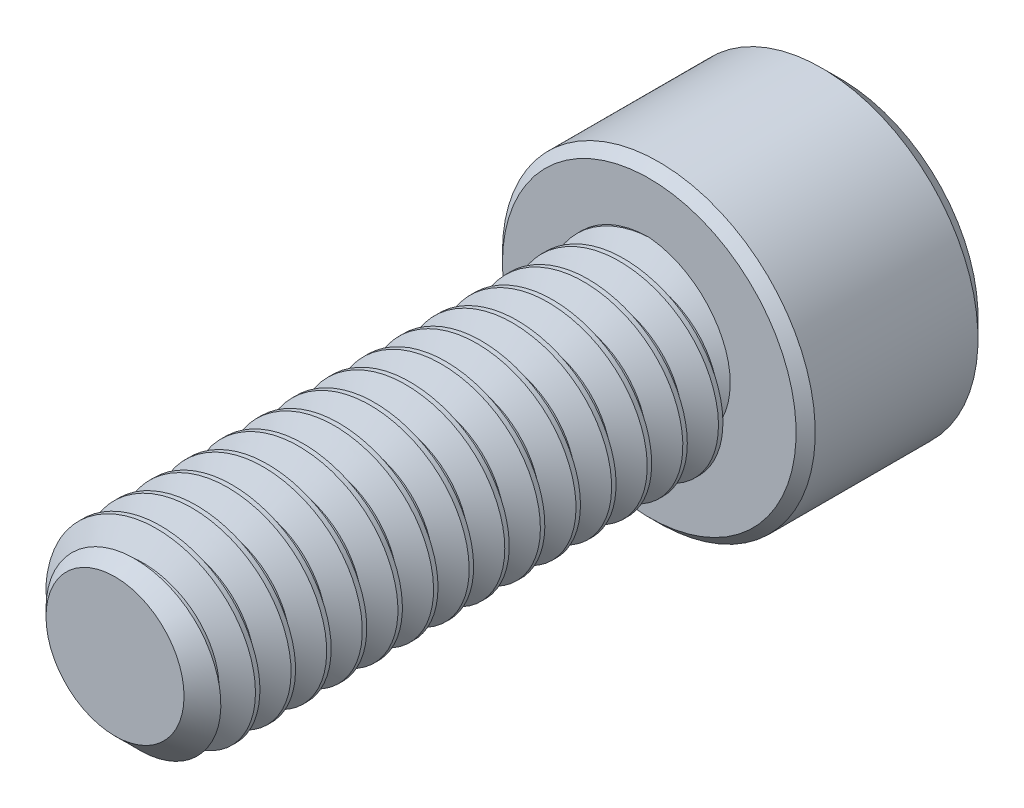
SolidWorks part; units mm, degrees
ref_plane "Front Plane" through (0, 0, 0) normal (0, 0, 1) x (1, 0, 0)
ref_plane "Top Plane" through (0, 0, 0) normal (0, 1, 0) x (1, 0, 0)
ref_plane "Right Plane" through (0, 0, 0) normal (1, 0, 0) x (0, 0, -1)
sketch "Sketch1" plane through (0, 0, 0) normal (0, 0, 1) x (1, 0, 0)
  line L0 (0, 1.4224) -> (0, -1.4224) construction
  circle A0 centre (0, 0) radius 1.4224
  dimension "OD" = 2.8448
extrude "Extrude1" add sketch "Sketch1" against normal blind 7.9375
sketch "Sketch2" plane through (0, 0, 0) normal (0, 0, 1) x (1, 0, 0)
  circle A0 centre (0, 0) radius 1.4224 construction
  circle A1 centre (0, 0) radius 1.4224
curve "Helix/Spiral1" pitch 0.5292 height 8.4667 radius 1.4224 centre (0, 0, 0) axis (0, 0, -1) start towards (0, 1, 0) parameters "pitch"=0.5292
chamfer "Chamfer3" distance 0.3969 angle 45 1 edges at (1.4224, 0, 0)
sketch "Sketch3" plane through (0, 0, 0) normal (1, 0, 0) x (0, 0, -1)
  line L0 (-0.463, 1.4224) -> (-0.2646, 1.0787)
  line L1 (-0.2646, 1.0787) -> (-0.1984, 1.0787)
  line L2 (-0.1984, 1.0787) -> (0, 1.4224)
  line L3 (-0.463, 1.4224) -> (0, 1.4224)
  line L4 (-0.2315, 1.4224) -> (-0.2315, 1.0787) construction
  line L5 (-0.3638, 1.2505) -> (-0.0992, 1.2505) construction
  line L6 (0, 1.4224) -> (0, -1.4224) construction
  dimension "D1" = 0.0661
  dimension "D2" = 0.2646
  dimension "D3" = 60
sweep "Cut-Sweep1" cut profiles "Sketch3" path "Helix/Spiral1" align with end faces yes
sketch "Sketch6" plane through (0, 0, -7.9375) normal (0, 0, -1) x (-1, 0, 0)
  circle A0 centre (0, 0) radius 2.3241
  dimension "head dia" = 4.6482
extrude "Extrude2" add sketch "Sketch6" along normal blind 2.8448
sketch "Sketch7" plane through (0, 0, -10.7823) normal (0, 0, -1) x (-1, 0, 0)
  line L1 (0, 1.3748) -> (-1.1906, 0.6874)
  line L2 (-1.1906, 0.6874) -> (-1.1906, -0.6874)
  line L3 (-1.1906, -0.6874) -> (0, -1.3748)
  line L4 (0, -1.3748) -> (1.1906, -0.6874)
  line L5 (1.1906, -0.6874) -> (1.1906, 0.6874)
  line L6 (1.1906, 0.6874) -> (0, 1.3748)
  circle A0 centre (0, 0) radius 1.1906 construction
  dimension "hex dia" = 2.3813
extrude "Cut-Extrude1" cut sketch "Sketch7" against normal blind 1.7859
sketch "Sketch8" plane through (0, 0, -10.7823) normal (0, 0, -1) x (-1, 0, 0)
  circle A0 centre (0, 0) radius 1.3748
extrude "Cut-Extrude2" cut sketch "Sketch8" against normal blind 0.2845 draft 45
chamfer "Chamfer1" distance 0.2845 angle 45 1 edges at (-2.3241, 0, -10.7823)
chamfer "Chamfer2" distance 0.1422 angle 45 1 edges at (-2.3241, 0, -7.9375)
sketch "Sketch9" plane through (0, 0, 0) normal (1, 0, 0) x (0, 0, -1)
  line L0 (0, 1.4224) -> (0, -1.4224) construction
  line L1 (2.9104, 1.4224) -> (2.9104, -1.4224) construction
  line L2 (7.9375, 2.3241) -> (7.9375, -2.3241) construction
  line L3 (10.7823, 2.3241) -> (10.7823, -2.3241) construction
  line L4 (10.7823, 0) -> (0, 0) construction
  dimension "D1" = 2.9104
  dimension "D2" = 2.8448
  dimension "D3" = 4.6482
  dimension "D4" = 7.9375
equation "\"D3@Helix/Spiral1\" = \"screw length@Extrude1\"+\"pitch@Helix/Spiral1\""
equation "\"D1@Sketch3\" = \"pitch@Helix/Spiral1\"*.125"
equation "\"D2@Sketch3\" = \"pitch@Helix/Spiral1\"*.5"
equation "\"D1@Cut-Extrude1\" = \"hex dia@Sketch7\"*.75"
equation "\"D1@Chamfer1\" = \"head depth@Extrude2\"/10"
equation "\"D1@Sketch9\" = \"pitch@Helix/Spiral1\"*5.5"
equation "\"D1@Chamfer2\" = \"D1@Chamfer1\"/2"
equation "\"D1@Cut-Extrude2\" = \"D1@Chamfer2\"*2"
equation "\"D1@Chamfer3\" = \"pitch@Helix/Spiral1\"*.750"
equation "\"D2@Sketch9\" = \"head depth@Extrude2\""
equation "\"D3@Sketch9\" = \"head dia@Sketch6\""
equation "\"D4@Sketch9\" = \"screw length@Extrude1\""
